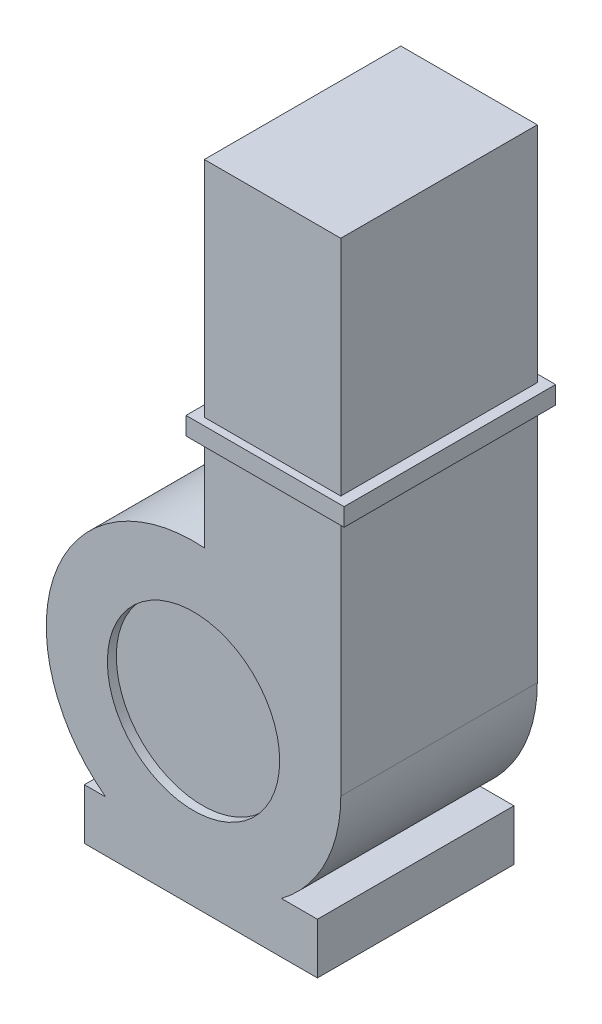
SolidWorks part; units mm, degrees
ref_plane "Front Plane" through (0, 0, 0) normal (0, 0, 1) x (1, 0, 0)
ref_plane "Top Plane" through (0, 0, 0) normal (0, 1, 0) x (1, 0, 0)
ref_plane "Right Plane" through (0, 0, 0) normal (1, 0, 0) x (0, 0, -1)
sketch "Sketch1" plane through (0, 0, 0) normal (0, 0, 1) x (1, 0, 0)
  line L1 (-20, 25) -> (20, 25)
  line L2 (-20, 25) -> (-20, -25)
  line L3 (-20, -25) -> (20, -25)
  line L4 (20, 25) -> (20, -25)
  line L5 (-20, 25) -> (-5.597, 6.9962) construction
  line L6 (-20, -25) -> (-13.9017, -17.3771) construction
  line L7 (1.2086, 18.5916) -> (16.4876, 18.5916)
  line L8 (1.2086, 18.5916) -> (1.2086, 7.9309)
  line L10 (16.4876, 18.5916) -> (16.4876, -8.5124)
  line L12 (14.8733, 18.5916) -> (20, 25) construction
  line L13 (13.9017, -17.3771) -> (20, -25) construction
  arc A0 (1.2086, 7.9309) -> (16.4876, -8.5124) centre (0, -8.5124) ccw
  point P0 (0, 0)
  dimension "D1" = 40
  dimension "D2" = 50
extrude "Boss-Extrude1" add sketch "Sketch1" along normal mid plane 22 contours L8 A0 L10 L7 region at (2.0308, -4.5273, 0)
sketch "Sketch2" plane through (0, 0, 11) normal (0, 0, 1) x (1, 0, 0)
  circle A0 centre (0, -8.5124) radius 9.6443
extrude "Cut-Extrude1" cut sketch "Sketch2" against normal blind 1
shell "Shell1" thickness 2 removed face at (8.8481, 18.5916, 0)
sketch "Sketch3" plane through (0, 0, 11) normal (0, 0, 1) x (1, 0, 0)
  line L1 (-12.2225, -21.744) -> (13.8705, -21.744)
  line L2 (-12.2225, -21.744) -> (-12.2225, -27.4432)
  line L3 (-12.2225, -27.4432) -> (13.8705, -27.4432)
  line L4 (13.8705, -21.744) -> (13.8705, -27.4432)
extrude "Boss-Extrude2" add sketch "Sketch3" against normal up to surface (22 mm away) up to face at (3.6165, 4.2893, -11)
sketch "Sketch4" plane through (0, 18.5916, 0) normal (0, 1, 0) x (1, 0, 0)
  line L1 (1.2086, 11) -> (16.4876, 11)
  line L2 (1.2086, 11) -> (1.2086, -11)
  line L3 (1.2086, -11) -> (16.4876, -11)
  line L4 (16.4876, 11) -> (16.4876, -11)
  line L5 (17.6962, -11.8406) -> (0, -11.8406)
  line L6 (17.6962, -11.8406) -> (17.6962, 11.8406)
  line L7 (17.6962, 11.8406) -> (0, 11.8406)
  line L8 (0, -11.8406) -> (0, 11.8406)
  line L9 (17.6962, -11.8406) -> (0, 11.8406) construction
  line L10 (17.6962, 11.8406) -> (0, -11.8406) construction
  point P6 (8.8481, 0)
extrude "Boss-Extrude3" add sketch "Sketch4" along normal blind 2 separate body
sketch "Sketch5" plane through (0, 20.5916, 0) normal (0, 1, 0) x (1, 0, 0)
  line L4 (16.4876, 11) -> (1.2086, 11)
  line L5 (1.2086, 11) -> (1.2086, -11)
  line L6 (1.2086, -11) -> (16.4876, -11)
  line L7 (16.4876, -11) -> (16.4876, 11)
  line L8 (16.4876, 11) -> (1.2086, 11)
  line L9 (1.2086, 11) -> (1.2086, -11)
  line L10 (1.2086, -11) -> (16.4876, -11)
  line L11 (16.4876, -11) -> (16.4876, 11)
  dimension "D1" = 0
extrude "Boss-Extrude4" add sketch "Sketch5" along normal blind 25 separate body
